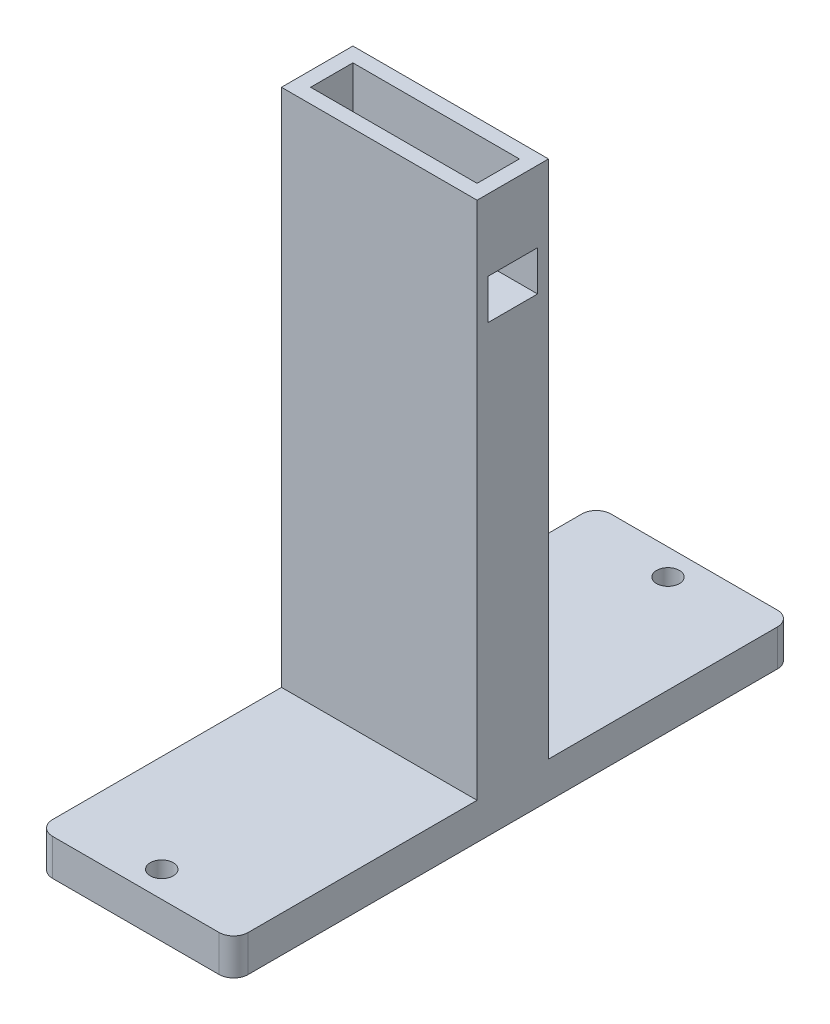
SolidWorks part; units mm, degrees
ref_plane "Front Plane" through (0, 0, 0) normal (0, 0, 1) x (1, 0, 0)
ref_plane "Top Plane" through (0, 0, 0) normal (0, 1, 0) x (1, 0, 0)
ref_plane "Right Plane" through (0, 0, 0) normal (1, 0, 0) x (0, 0, -1)
sketch "Sketch1" plane through (0, 0, 0) normal (0, 1, 0) x (1, 0, 0)
  line L0 (17.04, 6.223) -> (-17.04, 6.223)
  line L1 (14.5, -3.683) -> (-14.5, -3.683) construction
  line L2 (14.5, -3.683) -> (14.5, 3.683) construction
  line L3 (14.5, 3.683) -> (-14.5, 3.683) construction
  line L4 (-14.5, -3.683) -> (-14.5, 3.683) construction
  line L5 (14.5, -3.683) -> (-14.5, 3.683) construction
  line L6 (14.5, 3.683) -> (-14.5, -3.683) construction
  line L7 (-17.04, -6.223) -> (-17.04, 6.223)
  line L8 (17.04, -6.223) -> (-17.04, -6.223)
  line L9 (17.04, -6.223) -> (17.04, 6.223)
  line L10 (-3.2732, 0) -> (4.5518, 0) construction
  line L11 (-17.04, 6.223) -> (17.04, 6.223)
  line L12 (-17.04, 6.223) -> (-17.04, 46.101)
  line L13 (-14.5, 48.641) -> (14.5, 48.641)
  line L14 (17.04, 6.223) -> (17.04, 46.101)
  line L15 (17.04, -6.223) -> (17.04, -46.101)
  line L16 (-14.5, -48.641) -> (14.5, -48.641)
  line L17 (-17.04, -6.223) -> (-17.04, -46.101)
  arc A0 (14.5, 48.641) -> (17.04, 46.101) centre (14.5, 46.101) cw
  arc A1 (-17.04, 46.101) -> (-14.5, 48.641) centre (-14.5, 46.101) cw
  arc A2 (14.5, -48.641) -> (17.04, -46.101) centre (14.5, -46.101) ccw
  arc A3 (-17.04, -46.101) -> (-14.5, -48.641) centre (-14.5, -46.101) ccw
  circle A4 centre (-0.022, 44.101) radius 2
  circle A5 centre (-0.022, -44.101) radius 2
  point P0 (0, 0)
  point P20 (-17.04, 48.641)
  dimension "D5" = 2.54
  dimension "D6" = 4
  dimension "D1" = 29
  dimension "D2" = 7.366
  dimension "D4" = 42.418
  dimension "D7" = 17.018
  dimension "D3" = 2.54
extrude "Boss-Extrude1" add sketch "Sketch1" along normal blind 6.35 contours A1 L12 L0 L14 A0 L13 A4 | L17 A3 L16 A2 L15 L8 A5 region at (0.0002, 0, -27.2456) region at (0.0002, 0, 27.2456)
extrude "Boss-Extrude2" add sketch "Sketch1<3>" along normal blind 77.5 contours L8 L9 L0 L7 region at (0, 0, 0)
sketch "Sketch1<3>" plane through (0, 0, 0) normal (0, 1, 0) x (1, 0, 0) same geometry as "Sketch1"
sketch "Sketch2" plane through (0, 77.5, 0) normal (0, 1, 0) x (1, 0, 0)
  line L1 (-17.04, 6.223) -> (17.04, 6.223)
  line L2 (-17.04, 6.223) -> (-17.04, -6.223)
  line L3 (-17.04, -6.223) -> (17.04, -6.223)
  line L4 (17.04, 6.223) -> (17.04, -6.223)
  line L5 (-14.5, 3.683) -> (14.5, 3.683)
  line L6 (-14.5, 3.683) -> (-14.5, -3.683)
  line L7 (-14.5, -3.683) -> (14.5, -3.683)
  line L8 (14.5, 3.683) -> (14.5, -3.683)
extrude "Boss-Extrude3" add sketch "Sketch2" along normal blind 19.4
sketch "Sketch3" plane through (17.04, 0, 0) normal (1, 0, 0) x (0, 0, -1)
  line L0 (-6.223, 0) -> (6.223, 0) construction
  line L1 (-4.318, 84.463) -> (4.318, 84.463)
  line L2 (-4.318, 84.463) -> (-4.318, 77.478)
  line L3 (-4.318, 77.478) -> (4.318, 77.478)
  line L4 (4.318, 84.463) -> (4.318, 77.478)
  line L5 (-6.223, 96.9) -> (-6.223, 6.35) construction
  line L6 (6.223, 96.9) -> (6.223, 6.35) construction
  dimension "D1" = 77.478
  dimension "D2" = 1.905
  dimension "D3" = 1.905
  dimension "D4" = 6.985
extrude "Cut-Extrude1" cut sketch "Sketch3" against normal blind 13.97
sketch "Sketch4" plane through (0, 77.5, 0) normal (0, 1, 0) x (1, 0, 0)
  line L0 (14.5, -3.683) -> (-14.5, -3.683) construction
  line L1 (-14.5, 3.683) -> (-9.5, 3.683)
  line L2 (-14.5, 3.683) -> (-14.5, -3.683)
  line L3 (-14.5, -3.683) -> (-9.5, -3.683)
  line L4 (-9.5, 3.683) -> (-9.5, -3.683)
  dimension "D1" = 5
extrude "Boss-Extrude4" add sketch "Sketch4" along normal blind 3.2
